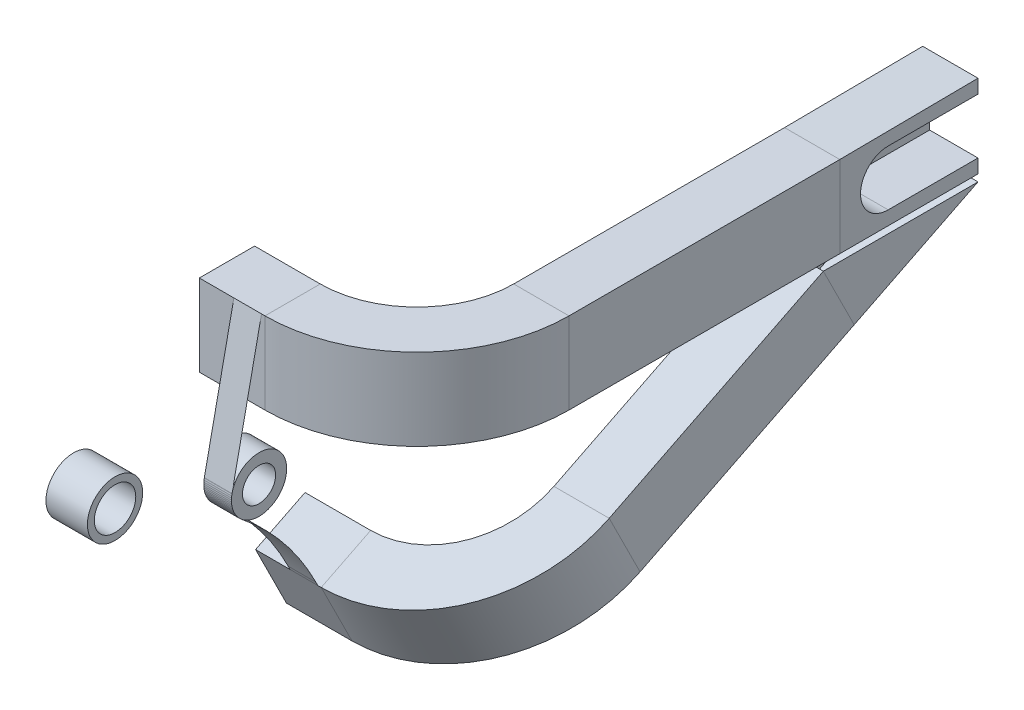
SolidWorks part; units mm, degrees
note: '?' marks a value the reader was unsure of. The reader was unsure of these and kept them because the rebuilt part matched: shared geometry of "Szkic - insert - tylne koło<6>", "Szkic5<4>".
ref_plane "Płaszczyzna przednia" through (0, 0, 0) normal (0, 0, 1) x (1, 0, 0)
ref_plane "Płaszczyzna górna" through (0, 0, 0) normal (0, 1, 0) x (1, 0, 0)
ref_plane "Płaszczyzna prawa" through (0, 0, 0) normal (1, 0, 0) x (0, 0, -1)
sketch "Baza - płaszczyzna prawa" plane through (0, 0, 0) normal (1, 0, 0) x (0, 0, -1)
  line L0 (0, 0) -> (512, 0) construction
  line L1 (0, 0) -> (512, 0) construction
  line L2 (144.2, 0) -> (144.2, -77) construction
  line L3 (90, 0) -> (90, 100) construction
  line L4 (200, 0) -> (200, 140) construction
  arc A2 (440.6668, 297.4126) -> (440.6668, -297.4126) centre (487, 0) ccw
  dimension "D3" = 90
  dimension "D4" = 100
  dimension "D5" = 301
  dimension "D1" = 77
  dimension "D2" = 144.2
  dimension "D6" = 200
  dimension "D7" = 140
sketch "Szkic1" plane through (0, 0, 0) normal (0, 1, 0) x (1, 0, 0)
  line L0 (0, 0) -> (0, 512) construction
  line L1 (0, 0) -> (0, 512) construction
  line L2 (117.5, 186) -> (-117.5, 186) construction
  line L3 (117.5, 186) -> (-117.5, 186) construction
  arc A0 (-89, 275) -> (89, 275) centre (0, 275) ccw
  point P7 (0, 186)
  dimension "D1" = 89
  dimension "D2" = 89
sketch "Baza - płaszczyzna górna" plane through (0, 0, 0) normal (0, 1, 0) x (1, 0, 0)
  line L0 (0, 0) -> (0, 512) construction
  line L1 (117.5, 144.2) -> (-117.5, 144.2) construction
  line L2 (135, 0) -> (-135, 0) construction
  line L3 (-117.5, 512) -> (117.5, 512) construction
  line L4 (-117.5, 512) -> (-117.5, 144.2) construction
  line L5 (117.5, 512) -> (117.5, 144.2) construction
  line L6 (117.5, 186) -> (-117.5, 186) construction
  line L7 (135, 22.5) -> (135, -22.5) construction
  line L8 (-135, 22.5) -> (-135, -22.5) construction
  line L9 (117.5, 512) -> (125, 512) construction
  line L10 (125, 512) -> (125, 144.2) construction
  line L11 (125, 144.2) -> (117.5, 144.2) construction
  point P2 (0, 487)
  point P7 (0, 0)
  point P10 (0, 512)
  point P12 (0, 144.2)
  point P16 (135, 0)
  dimension "D1" = 512
  dimension "D2" = 144.2
  dimension "D3" = 270
  dimension "D4" = 235
  dimension "D5" = 326
  dimension "D6" = 45
  dimension "D7" = 25
  dimension "D8" = 125
ref_plane "Powierzchnia styku z ramą" through (135, 0, 0) normal (1, 0, 0) x (0, 0, -1)
sketch "Szkic - insert - rama" plane through (135, 0, 0) normal (1, 0, 0) x (0, 0, -1)
  circle A0 centre (0, 0) radius 20
  circle A1 centre (0, 0) radius 15
  dimension "D1" = 40
  dimension "D2" = 30
ref_plane "Powierzchnia graniczna koła" through (125, 0, 0) normal (1, 0, 0) x (0, 0, -1)
ref_plane "Płaszczyzna pracy łańcucha" through (100, 0, 0) normal (1, 0, 0) x (0, 0, -1)
sketch "Łańcuch - baza" plane through (100, 0, 0) normal (1, 0, 0) x (0, 0, -1)
  line L0 (0, 0) -> (-72.2803, -23.4853) construction
  line L1 (0, 0) -> (512, 0) construction
  line L2 (0, 0) -> (-217.9404, 0) construction
  line L3 (0, 0) -> (-217.562, -40.3227) construction
  dimension "D1" = 76
  dimension "D2" = 162
  dimension "D3" = 10.5
sketch "Łańcuch - zarys" plane through (100, 0, 0) normal (1, 0, 0) x (0, 0, -1)
  line L0 (-75.0403, -1.6591) -> (502.9674, 71.4312)
  line L1 (-83.7478, 33.3697) -> (482.2437, 147.529)
  line L2 (-72.2803, -23.4853) -> (512, 0) construction
  line L3 (-79.1476, -81.0773) -> (494.1805, -149.4413)
  line L4 (-73.2796, -45.4626) -> (508.7296, -71.9257)
  circle A0 centre (-72.2803, -23.4853) radius 22
  circle A1 centre (512, 0) radius 72
  arc A2 (-83.7478, 33.3697) -> (-79.1476, -81.0773) centre (-72.2803, -23.4853) ccw
  arc A3 (494.1805, -149.4413) -> (482.2437, 147.529) centre (512, 0) ccw
  point P0 (-72.2803, -23.4853)
  point P2 (512, 0)
  dimension "D1" = 44
  dimension "D2" = 144
  dimension "D3" = 116
  dimension "D4" = 301
sketch "Szkic otwór łańcuch" plane through (0, 0, 0) normal (0, 0, 1) x (1, 0, 0)
  line L3 (100, -130) -> (110, -130)
  line L13 (115, -125) -> (115, -45)
  line L14 (110, -40) -> (100, -40)
  line L15 (95, -45) -> (95, -125)
  arc A0 (100, -130) -> (95, -125) centre (100, -125) cw
  arc A1 (110, -130) -> (115, -125) centre (110, -125) ccw
  arc A2 (115, -45) -> (110, -40) centre (110, -45) ccw
  arc A3 (100, -40) -> (95, -45) centre (100, -45) ccw
  dimension "D1" = 5
  dimension "D2" = 95
  dimension "D3" = 20
  dimension "D4" = 40
  dimension "D5" = 90
surface "Opona"
ref_axis "Oś tynego koła" through (-117.5, 0, -512) along (1, 0, 0)?
ref_axis "Oś mocowania do ramy" through (135, 0, 0) along (-1, 0, 0)?
ref_axis "Oś mocowania linkage" through (0, -77, -144.2) along (1, 0, 0)?
sketch "Szkic - insert - linkage" plane through (0, 0, 0) normal (1, 0, 0) x (0, 0, -1)
  circle A0 centre (144.2, -77) radius 12
  circle A1 centre (144.2, -77) radius 20
  dimension "D1" = 40
  dimension "D2" = 24
sketch "Szkic - insert - tylne koło" plane through (125, 0, 0) normal (1, 0, 0) x (0, 0, -1)
  line L0 (487, 20) -> (552, 20)
  line L1 (512, 0) -> (144.2, 0) construction
  line L2 (487, -20) -> (552, -20)
  line L3 (537, 8) -> (487, 8)
  line L4 (537, -8) -> (487, -8)
  line L6 (552, -30) -> (552, -20)
  line L7 (552, -30) -> (452, -30)
  line L8 (452, -30) -> (452, 29.0445)
  line L9 (452, 29.0445) -> (552, 30)
  line L11 (552, 20) -> (552, -20)
  line L12 (552, 20) -> (552, 30)
  arc A1 (487, 8) -> (487, -8) centre (487, 0) ccw
  arc A2 (537, -8) -> (537, 8) centre (537, 0) ccw
  arc A3 (487, 20) -> (487, -20) centre (487, 0) ccw
  dimension "D1" = 40
  dimension "D3" = 8
  dimension "D2" = 65
  dimension "D4" = 487
  dimension "D5" = 537
  dimension "D6" = 60
  dimension "D7" = 10
  dimension "D8" = 100
  dimension "D9" = 29.0445
extrude "Tylne koło" add sketch "Szkic - insert - tylne koło" along normal blind 5 from offset 7.5 separate body contours A3 L0 L12 L9 L8 L7 L6 L2 | L0 A3 L2 L11 A2 L4 A1 L3 offset against normal yes
extrude "Tylene koło 2" add sketch "Szkic - insert - tylne koło<6>" along normal blind 35 from offset 2.5 contours A3 L0 L12 L9 L8 L7 L6 L2 offset against normal yes
sketch "Szkic - insert - tylne koło<6>" plane through (125, 0, 0) normal (1, 0, 0) x (0, 0, -1) same geometry as "Szkic - insert - tylne koło"
extrude "Rama" add sketch "Szkic - insert - rama" against normal blind 30 from offset 50 separate body offset against normal yes
extrude "Linkage" add sketch "Szkic - insert - linkage" along normal blind 20 from offset 25 separate body
ref_plane "Płaszczyzna1" through (0, 0, -186) normal (0, 0, 1) x (1, 0, 0)
ref_point "Punkt1"
ref_plane "Płaszczyzna2" through (0, 87.7773, 0) normal (0, 1, 0) x (1, 0, 0)
ref_plane "Płaszczyzna5" through (0, 127.7773, 0) normal (0, 1, 0) x (1, 0, 0)
sketch "Szkic2" plane through (0, 0, 0) normal (1, 0, 0) x (0, 0, -1)
  line L0 (452, 29.0445) -> (222.4858, 143.6428) construction
  line L3 (552, 30) -> (552, 35) construction
  line L4 (552, 35) -> (244.8217, 188.3765) construction
  line L9 (552, 35) -> (440.0726, 35) construction
  line L10 (244.8217, 188.3765) -> (222.4858, 143.6428)
  line L11 (222.4858, 143.6428) -> (186.6988, 161.5115)
  line L12 (186.6988, 161.5115) -> (209.0347, 206.2452)
  line L13 (209.0347, 206.2452) -> (244.8217, 188.3765)
  arc A0 (440.6668, 297.4126) -> (440.6668, -297.4126) centre (487, 0) ccw construction
  point P3 (222.4858, 143.6428)
  point P9 (0, 0)
  dimension "D1" = 5
  dimension "D2" = 50
  dimension "D3" = 40
ref_plane "Płaszczyzna6" through (0, 35, 0) normal (0, 1, 0) x (1, 0, 0)
ref_plane "Płaszczyzna7" through (0, 35, -440.0726) normal (0, 0.4467, 0.8947) x (1, 0, 0)
ref_axis "Oś1" through (199.8374, 35, -440.0726) along (-1, 0, 0)?
sketch "Szkic3" plane through (0, 35, 0) normal (0, 1, 0) x (1, 0, 0)
  line L0 (117.5, 552) -> (157.5, 552)
  line L1 (157.5, 552) -> (157.5, 440.0726)
  line L2 (117.5, 552) -> (117.5, 440.0726)
  line L3 (117.5, 512) -> (117.5, 144.2) construction
  line L4 (117.5, 440.0726) -> (157.5, 440.0726)
  line L5 (199.8374, 440.0726) -> (71.3754, 440.0726) construction
sketch "Szkic5" plane through (0, 35, -440.0726) normal (0, 0.4467, 0.8947) x (1, 0, 0)
  line L0 (157.5, 0) -> (117.5, 0)
  line L1 (117.5, 0) -> (117.5, 50)
  line L2 (117.5, 50) -> (117.5, 0) construction
  line L3 (117.5, 50) -> (157.5, 50)
  line L4 (157.5, 50) -> (157.5, 0) construction
  line L5 (157.5, 50) -> (157.5, 0)
  dimension "D1" = 50
ref_plane "Płaszczyzna10" through (0, 203.8982, -101.8079) normal (0, -0.8947, 0.4467) x (-1, 0, 0)
sketch "Szkic6" plane through (0, 203.8982, -101.8079) normal (0, -0.8947, 0.4467) x (-1, 0, 0)
  line L0 (-157.5, 378.0867) -> (-157.5, 204.8846)
  line L1 (0, 94.8846) -> (-47.5, 94.8846)
  arc A0 (-157.5, 204.8846) -> (-47.5, 94.8846) centre (-47.5, 204.8846) ccw
  point P7 (-157.5, 378.0867)
  dimension "D1" = 110
surface "Powierzchnia-Wyciągnięcie po ścieżce1"
surface "Powierzchnia-Wyciągnięcie po profilach1"
sketch "Szkic5<4>" plane through (0, 35, -440.0726) normal (0, 0.4467, 0.8947) x (1, 0, 0) same geometry as "Szkic5"
mirror "Lustro3" about plane through (0, 0, 0) normal (0, 1, 0) of bodies 255 254
sketch "Szkic9" plane through (0, 0, 0) normal (0, 1, 0) x (1, 0, 0)
  line L0 (117.5, 452) -> (117.5, 256)
  line L1 (0, 186) -> (47.5, 186)
  line L2 (117.5, 186) -> (-117.5, 186) construction
  arc A0 (47.5, 186) -> (117.5, 256) centre (47.5, 256) ccw
  dimension "D1" = 70
ref_plane "Płaszczyzna13" through (0, 0, -452) normal (0, 0, 1) x (1, 0, 0)
sketch "Szkic10" plane through (0, 0, -452) normal (0, 0, 1) x (1, 0, 0)
  line L0 (117.5, -30) -> (117.5, 29.0445) construction
  line L1 (157.5, -30) -> (117.5, -30) construction
  line L2 (157.5, -30) -> (157.5, 29.0445) construction
  line L3 (157.5, 29.0445) -> (117.5, 29.0445) construction
  line L4 (117.5, -30) -> (117.5, 29.0445)
  line L5 (157.5, -30) -> (117.5, -30)
  line L6 (157.5, -30) -> (157.5, 29.0445)
  line L7 (157.5, 29.0445) -> (117.5, 29.0445)
surface "Powierzchnia-Wyciągnięcie po ścieżce2"
sketch "Szkic18" plane through (0, 0, 0) normal (1, 0, 0) x (0, 0, -1)
  line L0 (186.6988, -161.5115) -> (185.3196, -158.7493)
  line L2 (146, 29.0445) -> (124.6257, -72.8957)
  circle A0 centre (144.2, -77) radius 20 construction
  arc A1 (124.6257, -72.8957) -> (131.7533, -92.655) centre (144.2, -77) ccw
  arc A2 (185.3196, -158.7493) -> (131.7533, -92.655) centre (9.3452, -246.6147) ccw
  point P3 (0, 0)
  point P4 (0, 0)
  point P11 (131.164, -92.1678)
  point P12 (133.3812, -93.8212)
  point P13 (144.2, -97)
surface "Powierzchnia-Wyciągnięcie1" sketch "Szkic18" parameters "D1"=20, "D19"=25
